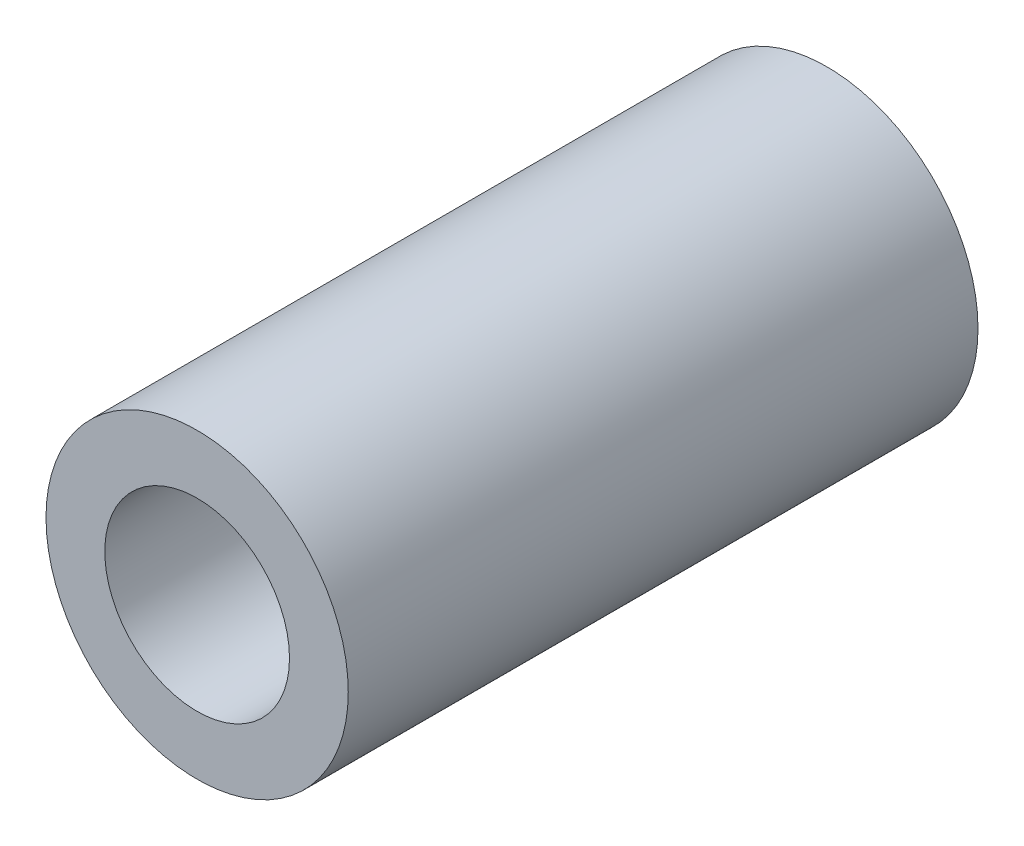
SolidWorks part; units mm, degrees
ref_plane "Front Plane" through (0, 0, 0) normal (0, 0, 1) x (1, 0, 0)
ref_plane "Top Plane" through (0, 0, 0) normal (0, 1, 0) x (1, 0, 0)
ref_plane "Right Plane" through (0, 0, 0) normal (1, 0, 0) x (0, 0, -1)
sketch "Sketch1" plane through (0, 0, 0) normal (0, 0, 1) x (1, 0, 0)
  circle A0 centre (0, 0) radius 1.8
  circle A1 centre (0, 0) radius 1.1
  dimension "D1" = 3.6
  dimension "D2" = 2.2
extrude "Boss-Extrude1" add sketch "Sketch1" along normal mid plane 7.5
